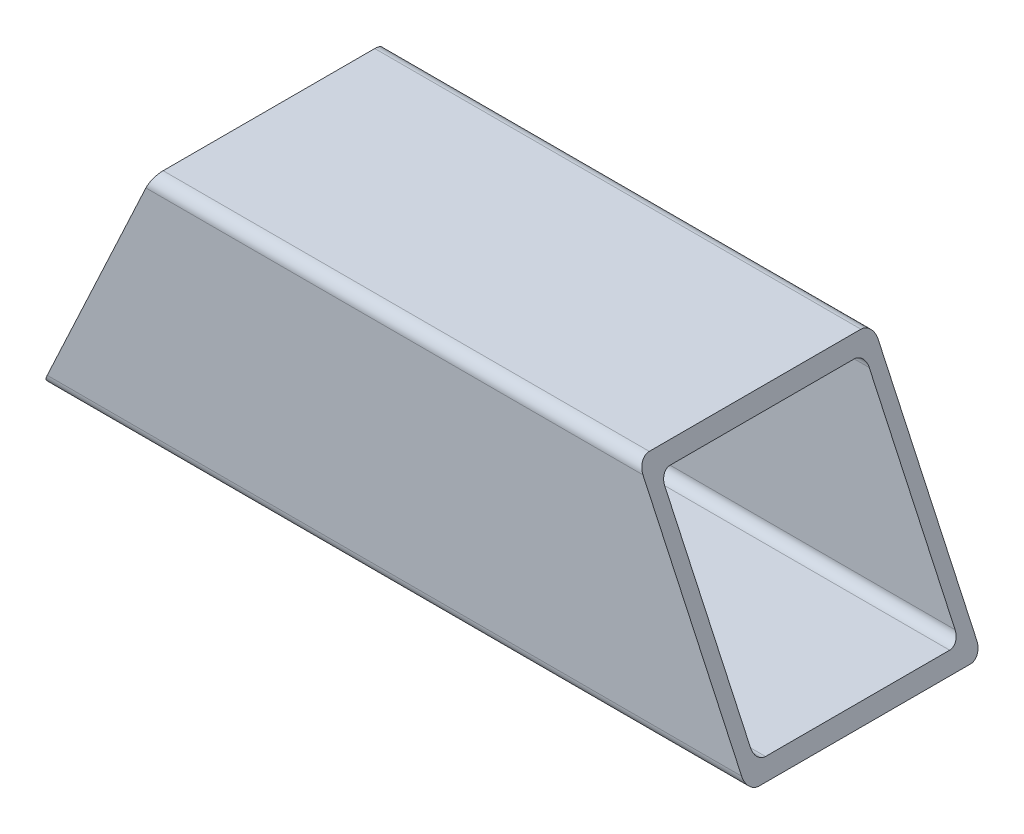
SolidWorks part; units mm, degrees
ref_plane "Front" through (0, 0, 0) normal (0, 0, 1) x (1, 0, 0)
ref_plane "Top" through (0, 0, 0) normal (0, 1, 0) x (1, 0, 0)
ref_plane "Right" through (0, 0, 0) normal (1, 0, 0) x (0, 0, -1)
sketch "Sketch1" plane through (0, 0, 0) normal (1, 0, 0) x (0, 0, -1)
  line L0 (-11.049, 0) -> (-12.7, 0) construction
  line L1 (11.43, -12.7) -> (-11.43, -12.7) construction
  line L2 (12.7, -11.43) -> (12.7, 11.43) construction
  line L3 (11.43, 12.7) -> (-11.43, 12.7) construction
  line L4 (-12.7, -11.43) -> (-12.7, 11.43) construction
  line L5 (12.7, -12.7) -> (-12.7, 12.7) construction
  line L6 (12.7, 12.7) -> (-12.7, -12.7) construction
  line L7 (9.9441, 11.049) -> (-9.9441, 11.049) construction
  line L8 (11.049, 9.9441) -> (11.049, -9.9441) construction
  line L9 (9.9441, -11.049) -> (-9.9441, -11.049) construction
  line L10 (-11.049, 9.9441) -> (-11.049, -9.9441) construction
  line L11 (11.049, 11.049) -> (-11.049, -11.049) construction
  line L12 (11.049, -11.049) -> (-11.049, 11.049) construction
  line L13 (0, -11.049) -> (0, -12.7) construction
  line L14 (11.049, -9.9441) -> (11.049, -12.7) construction
  line L15 (11.049, 0) -> (12.7, 0) construction
  line L16 (11.049, -12.7) -> (12.7, -12.7) construction
  arc A0 (-9.9441, -11.049) -> (-11.049, -9.9441) centre (-9.9441, -9.9441) cw construction
  arc A1 (11.049, -9.9441) -> (9.9441, -11.049) centre (9.9441, -9.9441) cw construction
  arc A2 (9.9441, 11.049) -> (11.049, 9.9441) centre (9.9441, 9.9441) cw construction
  arc A3 (-9.9441, 11.049) -> (-11.049, 9.9441) centre (-9.9441, 9.9441) ccw construction
  arc A4 (11.43, -12.7) -> (12.7, -11.43) centre (11.43, -11.43) ccw construction
  arc A5 (12.7, 11.43) -> (11.43, 12.7) centre (11.43, 11.43) ccw construction
  arc A6 (-11.43, 12.7) -> (-12.7, 11.43) centre (-11.43, 11.43) ccw construction
  arc A7 (-11.43, -12.7) -> (-12.7, -11.43) centre (-11.43, -11.43) cw construction
  point P0 (0, 0)
  point P6 (0, 0)
  dimension "D2" = 1.1049
  dimension "D3" = 1.27
  dimension "Outside Width" = 25.4
  dimension "Ouside Height" = 25.4
  dimension "Inside Height" = 22.098
  dimension "Wall Thickness" = 1.651
sketch "Sketch2" plane through (0, 0, 0) normal (0, 0, 1) x (1, 0, 0)
  line L0 (-38.1, 0) -> (38.1, 0) construction
  point P3 (-14.351, 0)
  point P4 (14.351, 0)
  dimension "Length" = 76.2
  dimension "D1" = 23.749
  dimension "D2" = 23.749
sketch "Sketch4" plane through (0, 0, 0) normal (1, 0, 0) x (0, 0, -1)
  line L8 (12.7, -11.43) -> (12.7, 11.43)
  line L9 (11.43, 12.7) -> (-11.43, 12.7)
  line L10 (-12.7, -11.43) -> (-12.7, 11.43)
  line L11 (11.43, -12.7) -> (-11.43, -12.7)
  line L12 (11.049, 9.9441) -> (11.049, -9.9441)
  line L13 (9.9441, -11.049) -> (-9.9441, -11.049)
  line L14 (-11.049, 9.9441) -> (-11.049, -9.9441)
  line L15 (9.9441, 11.049) -> (-9.9441, 11.049)
  arc A8 (12.7, 11.43) -> (11.43, 12.7) centre (11.43, 11.43) ccw
  arc A9 (-11.43, 12.7) -> (-12.7, 11.43) centre (-11.43, 11.43) ccw
  arc A10 (-12.7, -11.43) -> (-11.43, -12.7) centre (-11.43, -11.43) ccw
  arc A11 (11.43, -12.7) -> (12.7, -11.43) centre (11.43, -11.43) ccw
  arc A12 (9.9441, -11.049) -> (11.049, -9.9441) centre (9.9441, -9.9441) ccw
  arc A13 (-11.049, -9.9441) -> (-9.9441, -11.049) centre (-9.9441, -9.9441) ccw
  arc A14 (-9.9441, 11.049) -> (-11.049, 9.9441) centre (-9.9441, 9.9441) ccw
  arc A15 (11.049, 9.9441) -> (9.9441, 11.049) centre (9.9441, 9.9441) ccw
extrude "Boss-Extrude1" add sketch "Sketch4" along normal up to vertex (-38.1 mm away) and the other way up to vertex (-38.1 mm away) up to point (-38.1, 0, 0) other way up to point (38.1, 0, 0)
sketch "Sketch5" plane through (0, 0, 12.7) normal (0, 0, 1) x (1, 0, 0)
  line L0 (38.1, -12.7) -> (26.2558, 12.7)
  line L1 (38.1, 12.7) -> (-38.1, 12.7) construction
  line L2 (26.2558, 12.7) -> (38.1, 12.7)
  line L3 (38.1, 12.7) -> (38.1, -12.7)
  dimension "D1" = 25
extrude "Cut-Extrude1" cut sketch "Sketch5" against normal through all
mirror "Mirror1" about plane through (0, 0, 0) normal (1, 0, 0) of "Cut-Extrude1"
equation "\"D3@Sketch1\"=\"Outside Width@Sketch1\"*.05"
equation "\"D2@Sketch1\" = \"Inside Height@Sketch1\" * .05"
equation "\"D1@Sketch2\"=\"Outside Width@Sketch1\"-\"Wall Thickness@Sketch1\""
equation "\"D2@Sketch2\"=\"D1@Sketch2\""
